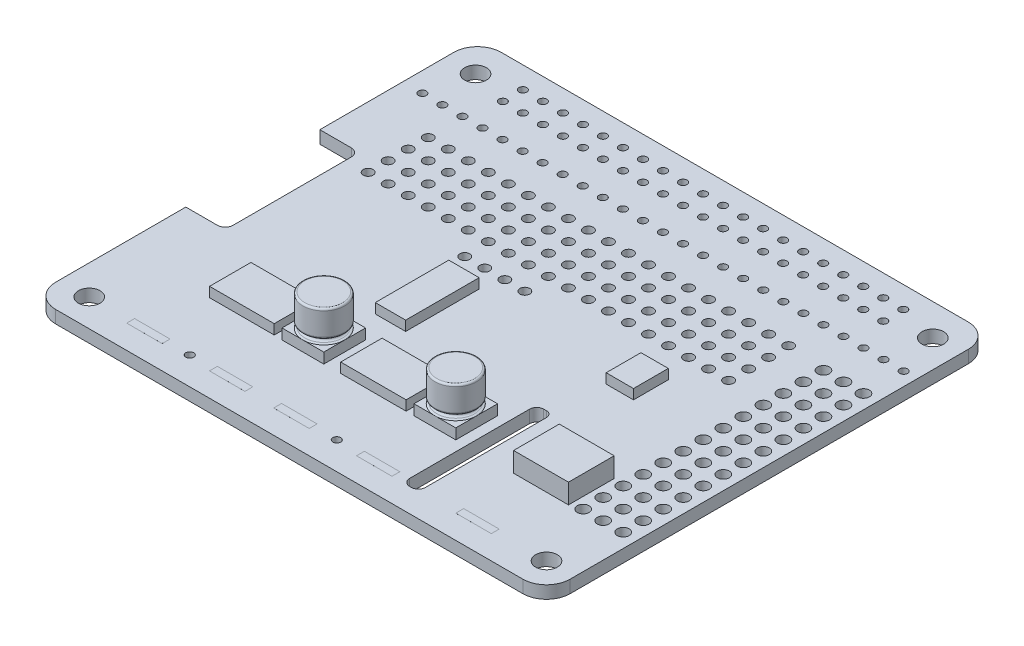
SolidWorks part; units mm, degrees
ref_plane "Front Plane" through (0, 0, 0) normal (0, 0, 1) x (1, 0, 0)
ref_plane "Top Plane" through (0, 0, 0) normal (0, 1, 0) x (1, 0, 0)
ref_plane "Right Plane" through (0, 0, 0) normal (1, 0, 0) x (0, 0, -1)
sketch "Sketch1" plane through (0, 0, 0) normal (0, 1, 0) x (1, 0, 0)
  line L1 (-72.0204, 27.4034) -> (-12.7704, 27.4034)
  line L2 (-75.0204, 24.4034) -> (-75.0204, -26.0966)
  line L3 (-72.0204, -29.0966) -> (-12.7704, -29.0966)
  line L4 (-9.7704, 24.4034) -> (-9.7704, -26.0966)
  line L5 (-75.0204, 7.4034) -> (-71.0204, 7.4034)
  line L6 (-75.0204, 7.4034) -> (-75.0204, -9.5966)
  line L7 (-75.0204, -9.5966) -> (-71.0204, -9.5966)
  line L8 (-70.0204, 6.4034) -> (-70.0204, -8.5966)
  line L9 (-29.7669, -9.0966) -> (-30.1204, -9.0966)
  line L10 (-29.0204, -9.8431) -> (-29.0204, -25.1966)
  line L11 (-29.9204, -26.0966) -> (-30.1204, -26.0966)
  line L12 (-31.0204, -9.9966) -> (-31.0204, -25.1966)
  arc A0 (-72.0204, -29.0966) -> (-75.0204, -26.0966) centre (-72.0204, -26.0966) cw
  arc A1 (-9.7704, -26.0966) -> (-12.7704, -29.0966) centre (-12.7704, -26.0966) cw
  arc A2 (-9.7704, 24.4034) -> (-12.7704, 27.4034) centre (-12.7704, 24.4034) ccw
  arc A3 (-72.0204, 27.4034) -> (-75.0204, 24.4034) centre (-72.0204, 24.4034) ccw
  arc A4 (-70.0204, -8.5966) -> (-71.0204, -9.5966) centre (-71.0204, -8.5966) cw
  arc A5 (-70.0204, 6.4034) -> (-71.0204, 7.4034) centre (-71.0204, 6.4034) ccw
  arc A6 (-29.0204, -25.1966) -> (-29.9204, -26.0966) centre (-29.9204, -25.1966) cw
  arc A7 (-30.1204, -26.0966) -> (-31.0204, -25.1966) centre (-30.1204, -25.1966) cw
  arc A8 (-30.1204, -9.0966) -> (-31.0204, -9.9966) centre (-30.1204, -9.9966) ccw
  arc A9 (-29.7669, -9.0966) -> (-29.0204, -9.8431) centre (-29.7669, -9.8431) cw
  circle A10 centre (-13.2704, -25.5966) radius 1.375
  circle A11 centre (-71.2704, -25.5966) radius 1.375
  circle A12 centre (-71.2704, 23.4034) radius 1.375
  circle A13 centre (-13.2704, 23.4034) radius 1.375
  point P6 (-75.0204, -29.0966)
  point P11 (-9.7704, 27.4034)
  point P14 (-75.0204, 27.4034)
  point P23 (-70.0204, 7.4034)
  point P30 (-29.0204, -26.0966)
  point P35 (-31.0204, -9.0966)
  point P38 (-29.0204, -9.0966)
  dimension "D3" = 3
  dimension "D7" = 1
  dimension "D12" = 0.9
  dimension "D13" = 0.7465
  dimension "D14" = 2.75
  dimension "D1" = 56.5
  dimension "D2" = 65.25
  dimension "D4" = 17
  dimension "D5" = 5
  dimension "D6" = 20
  dimension "D8" = 17
  dimension "D9" = 2
  dimension "D10" = 44
  dimension "D11" = 3
  dimension "D15" = 3.5
  dimension "D16" = 3.5
  dimension "D17" = 2
  dimension "D18" = 2
extrude "Board" add sketch "Sketch1" along normal blind 1.6 contours A5 L8 A4 L7 L2 A0 L3 A1 L4 A2 L1 A3 L5 A13 A12 A11 A10 L9 A9 L10 A6 L11 A7 L12 A8 region at (-41.7924, 0, 0.6811)
sketch "Sketch2" plane through (0, 1.6, 0) normal (0, 1, 0) x (1, 0, 0)
  line L8 (-70.0204, 6.4034) -> (-70.0204, -8.5966)
  line L9 (-71.0204, -9.5966) -> (-75.0204, -9.5966)
  line L10 (-75.0204, -9.5966) -> (-75.0204, -26.0966)
  line L11 (-72.0204, -29.0966) -> (-12.7704, -29.0966)
  line L12 (-9.7704, -26.0966) -> (-9.7704, 24.4034)
  line L13 (-12.7704, 27.4034) -> (-72.0204, 27.4034)
  line L14 (-75.0204, 24.4034) -> (-75.0204, 7.4034)
  line L15 (-75.0204, 7.4034) -> (-71.0204, 7.4034)
  line L16 (-70.0204, 6.4034) -> (-70.0204, -8.5966)
  line L17 (-71.0204, -9.5966) -> (-75.0204, -9.5966)
  line L18 (-75.0204, -9.5966) -> (-75.0204, -26.0966)
  line L19 (-72.0204, -29.0966) -> (-12.7704, -29.0966)
  line L20 (-9.7704, -26.0966) -> (-9.7704, 24.4034)
  line L21 (-12.7704, 27.4034) -> (-72.0204, 27.4034)
  line L22 (-75.0204, 24.4034) -> (-75.0204, 7.4034)
  line L23 (-75.0204, 7.4034) -> (-71.0204, 7.4034)
  circle A0 centre (-66.5204, 24.6534) radius 0.5
  circle A1 centre (-63.9804, 24.6534) radius 0.5
  circle A2 centre (-61.4404, 24.6534) radius 0.5
  circle A3 centre (-58.9004, 24.6534) radius 0.5
  circle A4 centre (-56.3604, 24.6534) radius 0.5
  circle A5 centre (-53.8204, 24.6534) radius 0.5
  arc A6 (-70.0204, 6.4034) -> (-71.0204, 7.4034) centre (-71.0204, 6.4034) ccw
  arc A7 (-71.0204, -9.5966) -> (-70.0204, -8.5966) centre (-71.0204, -8.5966) ccw
  arc A8 (-75.0204, -26.0966) -> (-72.0204, -29.0966) centre (-72.0204, -26.0966) ccw
  arc A9 (-12.7704, -29.0966) -> (-9.7704, -26.0966) centre (-12.7704, -26.0966) ccw
  arc A10 (-9.7704, 24.4034) -> (-12.7704, 27.4034) centre (-12.7704, 24.4034) ccw
  arc A11 (-72.0204, 27.4034) -> (-75.0204, 24.4034) centre (-72.0204, 24.4034) ccw
  arc A12 (-70.0204, 6.4034) -> (-71.0204, 7.4034) centre (-71.0204, 6.4034) ccw
  arc A13 (-71.0204, -9.5966) -> (-70.0204, -8.5966) centre (-71.0204, -8.5966) ccw
  arc A14 (-75.0204, -26.0966) -> (-72.0204, -29.0966) centre (-72.0204, -26.0966) ccw
  arc A15 (-12.7704, -29.0966) -> (-9.7704, -26.0966) centre (-12.7704, -26.0966) ccw
  arc A16 (-9.7704, 24.4034) -> (-12.7704, 27.4034) centre (-12.7704, 24.4034) ccw
  arc A17 (-72.0204, 27.4034) -> (-75.0204, 24.4034) centre (-72.0204, 24.4034) ccw
  circle A18 centre (-51.2804, 24.6534) radius 0.5
  circle A19 centre (-48.7404, 24.6534) radius 0.5
  circle A20 centre (-46.2004, 24.6534) radius 0.5
  circle A21 centre (-43.6604, 24.6534) radius 0.5
  circle A22 centre (-41.1204, 24.6534) radius 0.5
  circle A23 centre (-38.5804, 24.6534) radius 0.5
  circle A24 centre (-36.0404, 24.6534) radius 0.5
  circle A25 centre (-33.5004, 24.6534) radius 0.5
  circle A26 centre (-30.9604, 24.6534) radius 0.5
  circle A27 centre (-28.4204, 24.6534) radius 0.5
  circle A28 centre (-25.8804, 24.6534) radius 0.5
  circle A29 centre (-23.3404, 24.6534) radius 0.5
  circle A30 centre (-20.8004, 24.6534) radius 0.5
  circle A31 centre (-18.2604, 24.6534) radius 0.5
  circle A32 centre (-63.9804, 22.1134) radius 0.5
  circle A33 centre (-61.4404, 22.1134) radius 0.5
  circle A34 centre (-58.9004, 22.1134) radius 0.5
  circle A35 centre (-56.3604, 22.1134) radius 0.5
  circle A36 centre (-53.8204, 22.1134) radius 0.5
  circle A37 centre (-51.2804, 22.1134) radius 0.5
  circle A38 centre (-48.7404, 22.1134) radius 0.5
  circle A39 centre (-46.2004, 22.1134) radius 0.5
  circle A40 centre (-43.6604, 22.1134) radius 0.5
  circle A41 centre (-41.1204, 22.1134) radius 0.5
  circle A42 centre (-38.5804, 22.1134) radius 0.5
  circle A43 centre (-36.0404, 22.1134) radius 0.5
  circle A44 centre (-33.5004, 22.1134) radius 0.5
  circle A45 centre (-30.9604, 22.1134) radius 0.5
  circle A46 centre (-28.4204, 22.1134) radius 0.5
  circle A47 centre (-25.8804, 22.1134) radius 0.5
  circle A48 centre (-23.3404, 22.1134) radius 0.5
  circle A49 centre (-20.8004, 22.1134) radius 0.5
  circle A50 centre (-18.2604, 22.1134) radius 0.5
  circle A51 centre (-66.5204, 22.1134) radius 0.5
  circle A52 centre (-72.5204, 17.9034) radius 0.5
  circle A53 centre (-69.9766, 17.9034) radius 0.5
  circle A54 centre (-67.4329, 17.9034) radius 0.5
  circle A55 centre (-64.8891, 17.9034) radius 0.5
  circle A56 centre (-62.3454, 17.9034) radius 0.5
  circle A57 centre (-59.8016, 17.9034) radius 0.5
  circle A58 centre (-57.2579, 17.9034) radius 0.5
  circle A59 centre (-54.7141, 17.9034) radius 0.5
  circle A60 centre (-52.1704, 17.9034) radius 0.5
  circle A61 centre (-49.6266, 17.9034) radius 0.5
  circle A62 centre (-47.0829, 17.9034) radius 0.5
  circle A63 centre (-44.5391, 17.9034) radius 0.5
  circle A64 centre (-41.9954, 17.9034) radius 0.5
  circle A65 centre (-39.4516, 17.9034) radius 0.5
  circle A66 centre (-36.9079, 17.9034) radius 0.5
  circle A67 centre (-34.3641, 17.9034) radius 0.5
  circle A68 centre (-31.8204, 17.9034) radius 0.5
  circle A69 centre (-29.2766, 17.9034) radius 0.5
  circle A70 centre (-26.7329, 17.9034) radius 0.5
  circle A71 centre (-24.1891, 17.9034) radius 0.5
  circle A72 centre (-21.6454, 17.9034) radius 0.5
  circle A73 centre (-19.1016, 17.9034) radius 0.5
  circle A74 centre (-16.5579, 17.9034) radius 0.5
  circle A75 centre (-14.0141, 17.9034) radius 0.5
  circle A76 centre (-11.4704, 17.9034) radius 0.5
  circle A77 centre (-11.5604, 12.9034) radius 0.75
  circle A78 centre (-14.1004, 12.9034) radius 0.75
  circle A79 centre (-16.6404, 12.9034) radius 0.75
  circle A80 centre (-14.1004, 10.3634) radius 0.75
  circle A81 centre (-16.6404, 10.3634) radius 0.75
  circle A82 centre (-14.1004, 7.8234) radius 0.75
  circle A83 centre (-16.6404, 7.8234) radius 0.75
  circle A84 centre (-14.1004, 5.2834) radius 0.75
  circle A85 centre (-16.6404, 5.2834) radius 0.75
  circle A86 centre (-14.1004, 2.7434) radius 0.75
  circle A87 centre (-16.6404, 2.7434) radius 0.75
  circle A88 centre (-14.1004, 0.2034) radius 0.75
  circle A89 centre (-16.6404, 0.2034) radius 0.75
  circle A90 centre (-14.1004, -2.3366) radius 0.75
  circle A91 centre (-16.6404, -2.3366) radius 0.75
  circle A92 centre (-14.1004, -4.8766) radius 0.75
  circle A93 centre (-16.6404, -4.8766) radius 0.75
  circle A94 centre (-14.1004, -7.4166) radius 0.75
  circle A95 centre (-16.6404, -7.4166) radius 0.75
  circle A96 centre (-14.1004, -9.9566) radius 0.75
  circle A97 centre (-16.6404, -9.9566) radius 0.75
  circle A98 centre (-14.1004, -12.4966) radius 0.75
  circle A99 centre (-16.6404, -12.4966) radius 0.75
  circle A100 centre (-14.1004, -15.0366) radius 0.75
  circle A101 centre (-16.6404, -15.0366) radius 0.75
  circle A102 centre (-14.1004, -17.5766) radius 0.75
  circle A103 centre (-16.6404, -17.5766) radius 0.75
  circle A104 centre (-11.5604, 10.3634) radius 0.75
  circle A105 centre (-11.5604, 7.8234) radius 0.75
  circle A106 centre (-11.5604, 5.2834) radius 0.75
  circle A107 centre (-11.5604, 2.7434) radius 0.75
  circle A108 centre (-11.5604, 0.2034) radius 0.75
  circle A109 centre (-11.5604, -2.3366) radius 0.75
  circle A110 centre (-11.5604, -4.8766) radius 0.75
  circle A111 centre (-11.5604, -7.4166) radius 0.75
  circle A112 centre (-11.5604, -9.9566) radius 0.75
  circle A113 centre (-11.5604, -12.4966) radius 0.75
  circle A114 centre (-11.5604, -15.0366) radius 0.75
  circle A115 centre (-11.5604, -17.5766) radius 0.75
  circle A116 centre (-67.2704, 13.4034) radius 0.625
  circle A117 centre (-64.7304, 13.4034) radius 0.625
  circle A118 centre (-62.1904, 13.4034) radius 0.625
  circle A119 centre (-59.6504, 13.4034) radius 0.625
  circle A120 centre (-57.1104, 13.4034) radius 0.625
  circle A121 centre (-54.5704, 13.4034) radius 0.625
  circle A122 centre (-52.0304, 13.4034) radius 0.625
  circle A123 centre (-49.4904, 13.4034) radius 0.625
  circle A124 centre (-46.9504, 13.4034) radius 0.625
  circle A125 centre (-44.4104, 13.4034) radius 0.625
  circle A126 centre (-41.8704, 13.4034) radius 0.625
  circle A127 centre (-39.3304, 13.4034) radius 0.625
  circle A128 centre (-36.7904, 13.4034) radius 0.625
  circle A129 centre (-34.2504, 13.4034) radius 0.625
  circle A130 centre (-31.7104, 13.4034) radius 0.625
  circle A131 centre (-29.1704, 13.4034) radius 0.625
  circle A132 centre (-26.6304, 13.4034) radius 0.625
  circle A133 centre (-24.0904, 13.4034) radius 0.625
  circle A134 centre (-21.5504, 13.4034) radius 0.625
  circle A135 centre (-64.7304, 10.8634) radius 0.625
  circle A136 centre (-62.1904, 10.8634) radius 0.625
  circle A137 centre (-59.6504, 10.8634) radius 0.625
  circle A138 centre (-57.1104, 10.8634) radius 0.625
  circle A139 centre (-54.5704, 10.8634) radius 0.625
  circle A140 centre (-52.0304, 10.8634) radius 0.625
  circle A141 centre (-49.4904, 10.8634) radius 0.625
  circle A142 centre (-46.9504, 10.8634) radius 0.625
  circle A143 centre (-44.4104, 10.8634) radius 0.625
  circle A144 centre (-41.8704, 10.8634) radius 0.625
  circle A145 centre (-39.3304, 10.8634) radius 0.625
  circle A146 centre (-36.7904, 10.8634) radius 0.625
  circle A147 centre (-34.2504, 10.8634) radius 0.625
  circle A148 centre (-31.7104, 10.8634) radius 0.625
  circle A149 centre (-29.1704, 10.8634) radius 0.625
  circle A150 centre (-26.6304, 10.8634) radius 0.625
  circle A151 centre (-24.0904, 10.8634) radius 0.625
  circle A152 centre (-21.5504, 10.8634) radius 0.625
  circle A153 centre (-64.7304, 8.3234) radius 0.625
  circle A154 centre (-62.1904, 8.3234) radius 0.625
  circle A155 centre (-59.6504, 8.3234) radius 0.625
  circle A156 centre (-57.1104, 8.3234) radius 0.625
  circle A157 centre (-54.5704, 8.3234) radius 0.625
  circle A158 centre (-52.0304, 8.3234) radius 0.625
  circle A159 centre (-49.4904, 8.3234) radius 0.625
  circle A160 centre (-46.9504, 8.3234) radius 0.625
  circle A161 centre (-44.4104, 8.3234) radius 0.625
  circle A162 centre (-41.8704, 8.3234) radius 0.625
  circle A163 centre (-39.3304, 8.3234) radius 0.625
  circle A164 centre (-36.7904, 8.3234) radius 0.625
  circle A165 centre (-34.2504, 8.3234) radius 0.625
  circle A166 centre (-31.7104, 8.3234) radius 0.625
  circle A167 centre (-29.1704, 8.3234) radius 0.625
  circle A168 centre (-26.6304, 8.3234) radius 0.625
  circle A169 centre (-24.0904, 8.3234) radius 0.625
  circle A170 centre (-21.5504, 8.3234) radius 0.625
  circle A171 centre (-64.7304, 5.7834) radius 0.625
  circle A172 centre (-62.1904, 5.7834) radius 0.625
  circle A173 centre (-59.6504, 5.7834) radius 0.625
  circle A174 centre (-57.1104, 5.7834) radius 0.625
  circle A175 centre (-54.5704, 5.7834) radius 0.625
  circle A176 centre (-52.0304, 5.7834) radius 0.625
  circle A177 centre (-49.4904, 5.7834) radius 0.625
  circle A178 centre (-46.9504, 5.7834) radius 0.625
  circle A179 centre (-44.4104, 5.7834) radius 0.625
  circle A180 centre (-41.8704, 5.7834) radius 0.625
  circle A181 centre (-39.3304, 5.7834) radius 0.625
  circle A182 centre (-36.7904, 5.7834) radius 0.625
  circle A183 centre (-34.2504, 5.7834) radius 0.625
  circle A184 centre (-31.7104, 5.7834) radius 0.625
  circle A185 centre (-29.1704, 5.7834) radius 0.625
  circle A186 centre (-26.6304, 5.7834) radius 0.625
  circle A187 centre (-24.0904, 5.7834) radius 0.625
  circle A188 centre (-21.5504, 5.7834) radius 0.625
  circle A189 centre (-67.2704, 10.8634) radius 0.625
  circle A190 centre (-67.2704, 8.3234) radius 0.625
  circle A191 centre (-67.2704, 5.7834) radius 0.625
  circle A192 centre (-44.2704, 2.6534) radius 0.625
  circle A193 centre (-46.8104, 2.6534) radius 0.625
  circle A194 centre (-49.3504, 2.6534) radius 0.625
  circle A195 centre (-51.8904, 2.6534) radius 0.625
  circle A196 centre (-20.2704, -25.5966) radius 0.5
  circle A197 centre (-23.7704, -25.5966) radius 0.5
  circle A198 centre (-32.8704, -25.5966) radius 0.5
  circle A199 centre (-36.3704, -25.5966) radius 0.5
  circle A200 centre (-39.8704, -25.5966) radius 0.5
  circle A201 centre (-43.3704, -25.5966) radius 0.5
  circle A202 centre (-46.8704, -25.5966) radius 0.5
  circle A203 centre (-65.5204, -25.5966) radius 0.5
  circle A204 centre (-62.0204, -25.5966) radius 0.5
  circle A205 centre (-58.5204, -25.5966) radius 0.5
  circle A206 centre (-55.0204, -25.5966) radius 0.5
  circle A207 centre (-51.5204, -25.5966) radius 0.5
  dimension "D2" = 2.75
  dimension "D6" = 2.5
  dimension "D9" = 1.5
  dimension "D12" = 3
  dimension "D14" = 14
  dimension "D18" = 34.5
  dimension "D21" = 3.5
  dimension "D24" = 3.5
  dimension "D27" = 9.5
  dimension "D3" = 8.5
  dimension "D7" = 10.5
  dimension "D10" = 14.5
  dimension "D11" = 1.7
  dimension "D15" = 2.75
  dimension "D19" = 31.75
  dimension "D22" = 10.5
  dimension "D25" = 23.1
  dimension "D28" = 3.5
  dimension "D1" = 0
  dimension "D4" = 20
  dimension "D5" = 2
  dimension "D8" = 25
  dimension "D13" = 13
  dimension "D16" = 19
  dimension "D17" = 4
  dimension "D20" = 4
  dimension "D23" = 2
  dimension "D26" = 5
  dimension "D29" = 5
extrude "Some Holes" cut sketch "Sketch2" against normal blind 1.6 contours A114 | A83 | A103 | A102 | A115 | A100 | A101 | A99 | A98 | A113 | A112 | A96 | A97 | A95 | A94 | A111 | A110 | A92 | A93 | A91 | A90 | A109 | A108 | A88 | A89 | A87 | A86 | A107 | A106 | A84 | A85 | A82 | A105 | A104 | A77 | A80 | A81 | A79 | A78 | A76 | A75 | A74 | A73 | A72 | A50 | A31 | A49 | A30 | A48 | A29 | A71 | A70 | A47 | A28 | A27 | A46 | A69 | A68 | A45 | A26 | A67 | A44 | A25 | A66 | A43 | A24 | A65 | A42 | A23 | A64 | A41 | A22 | A63 | A40 | A21 | A20 | A39 | A62 | A61 | A38 | A19 | A18 | A37 | A60 | A59 | A36 | A5 | A4 | A35 | A58 | A57 | A34 | A3 | A2 | A33 | A56 | A55 | A32 | A1 | A0 region at (-16.6404, 1.6, -7.8234) region at (-11.5604, 1.6, 15.0366)
extrude "Remaining Holes" cut sketch "Sketch2<4>" against normal blind 1.6 contours A51 | A54 | A53 | A52 | A116 | A117 | A118 | A119 | A120 | A121 | A122 | A123 | A124 | A125 | A126 | A127 | A128 | A129 | A130 | A131 | A132 | A133 | A134 | A152 | A170 | A188 | A187 | A169 | A151 | A150 | A168 | A186 | A167 | A185 | A149 | A148 | A166 | A184 | A183 | A165 | A147 | A146 | A164 | A182 | A181 | A163 | A145 | A144 | A162 | A180 | A192 | A193 | A194 | A195 | A179 | A161 | A143 | A142 | A160 | A178 | A177 | A159 | A141 | A140 | A158 | A176 | A175 | A157 | A139 | A138 | A156 | A174 | A173 | A155 | A137 | A136 | A154 | A172 | A171 | A153 | A135 | A189 | A190 | A191 | A196 | A197 | A198 | A199 | A200 | A201 | A202 | A207 | A206 | A205 | A204 | A203
sketch "Sketch2<4>" plane through (0, 1.6, 0) normal (0, 1, 0) x (1, 0, 0) same geometry as "Sketch2"
sketch "Sketch3" plane through (0, 1.6, 0) normal (0, 1, 0) x (1, 0, 0)
  line L1 (-63.5566, -12.7994) -> (-55.3553, -12.7994)
  line L2 (-63.5566, -12.7994) -> (-63.5566, -18.049)
  line L3 (-63.5566, -18.049) -> (-55.3553, -18.049)
  line L4 (-55.3553, -12.7994) -> (-55.3553, -18.049)
  line L5 (-46.9235, -12.7994) -> (-38.6242, -12.7994)
  line L6 (-46.9235, -12.7994) -> (-46.9235, -18.049)
  line L7 (-46.9235, -18.049) -> (-38.6242, -18.049)
  line L8 (-38.6242, -12.7994) -> (-38.6242, -18.049)
  line L9 (-24.9943, -12.2493) -> (-18.0305, -12.2493)
  line L10 (-24.9943, -12.2493) -> (-24.9943, -18.049)
  line L11 (-24.9943, -18.049) -> (-18.0305, -18.049)
  line L12 (-18.0305, -12.2493) -> (-18.0305, -18.049)
  line L13 (-28.9097, 2.0257) -> (-25.4441, 2.0257)
  line L14 (-28.9097, 2.0257) -> (-28.9097, -2.3878)
  line L15 (-28.9097, -2.3878) -> (-25.4441, -2.3878)
  line L16 (-25.4441, 2.0257) -> (-25.4441, -2.3878)
  line L17 (-51.2629, 0) -> (-47.4092, 0)
  line L18 (-51.2629, 0) -> (-51.2629, -9.3248)
  line L19 (-51.2629, -9.3248) -> (-47.4092, -9.3248)
  line L20 (-47.4092, 0) -> (-47.4092, -9.3248)
  dimension "D1" = 5.2496
  dimension "D2" = 8.2013
  dimension "D3" = 5.2496
  dimension "D4" = 8.2993
  dimension "D5" = 5.7997
  dimension "D6" = 6.9638
  dimension "D7" = 4.4135
  dimension "D8" = 3.4656
  dimension "D9" = 9.3248
  dimension "D10" = 3.8537
extrude "ICs" add sketch "Sketch3" along normal blind 1.25 contours L8 L5 L6 L7 | L4 L1 L2 L3 | L16 L13 L14 L15 | L18 L17 L20 L19 region at (-59.456, 1.6, 15.4242) region at (-42.7739, 1.6, 15.4242) region at (-27.1769, 1.6, 0.181)
extrude "Voltage Regulator" add sketch "Sketch3<5>" along normal blind 2.5 contours L11 L12 L9 L10
sketch "Sketch3<5>" plane through (0, 1.6, 0) normal (0, 1, 0) x (1, 0, 0) same geometry as "Sketch3"
sketch "Sketch4" plane through (0, 1.6, 0) normal (0, 1, 0) x (1, 0, 0)
  line L0 (-31.0204, -9.9966) -> (-31.0204, -25.1966) construction
  line L1 (-54.3204, -18.0966) -> (-49.0204, -18.0966)
  line L2 (-54.3204, -18.0966) -> (-54.3204, -12.7966)
  line L3 (-54.3204, -12.7966) -> (-49.0204, -12.7966)
  line L4 (-49.0204, -18.0966) -> (-49.0204, -12.7966)
  line L5 (-32.3204, -18.0544) -> (-37.6204, -18.0544)
  line L6 (-32.3204, -18.0544) -> (-32.3204, -12.7544)
  line L7 (-32.3204, -12.7544) -> (-37.6204, -12.7544)
  line L8 (-37.6204, -18.0544) -> (-37.6204, -12.7544)
  line L9 (-72.0204, -29.0966) -> (-12.7704, -29.0966) construction
  dimension "D1" = 5.3
  dimension "D2" = 5.3
  dimension "D3" = 5.3
  dimension "D4" = 5.3
  dimension "D5" = 11.4
  dimension "D6" = 1.3
  dimension "D7" = 11
extrude "Cap Base" add sketch "Sketch4" along normal blind 1.32
sketch "Sketch5" plane through (0, 2.92, 0) normal (0, 1, 0) x (1, 0, 0)
  line L0 (-54.3204, -15.4466) -> (-49.0204, -15.4466)
  line L1 (-51.6704, -12.7966) -> (-51.6704, -18.0966)
  line L2 (-34.9704, -12.7544) -> (-34.9704, -18.0544)
  line L3 (-37.6204, -15.4044) -> (-32.3204, -15.4044)
  line L4 (-54.3204, -12.7966) -> (-54.3204, -18.0966)
  line L5 (-54.3204, -18.0966) -> (-49.0204, -18.0966)
  line L6 (-49.0204, -18.0966) -> (-49.0204, -12.7966)
  line L7 (-49.0204, -12.7966) -> (-54.3204, -12.7966)
  line L8 (-54.3204, -12.7966) -> (-54.3204, -18.0966)
  line L9 (-54.3204, -18.0966) -> (-49.0204, -18.0966)
  line L10 (-49.0204, -18.0966) -> (-49.0204, -12.7966)
  line L11 (-49.0204, -12.7966) -> (-54.3204, -12.7966)
  line L12 (-32.3204, -18.0544) -> (-32.3204, -12.7544)
  line L13 (-32.3204, -12.7544) -> (-37.6204, -12.7544)
  line L14 (-37.6204, -12.7544) -> (-37.6204, -18.0544)
  line L15 (-37.6204, -18.0544) -> (-32.3204, -18.0544)
  line L16 (-32.3204, -18.0544) -> (-32.3204, -12.7544)
  line L17 (-32.3204, -12.7544) -> (-37.6204, -12.7544)
  line L18 (-37.6204, -12.7544) -> (-37.6204, -18.0544)
  line L19 (-37.6204, -18.0544) -> (-32.3204, -18.0544)
  circle A0 centre (-51.6704, -15.4466) radius 2.65
  circle A1 centre (-34.9704, -15.4044) radius 2.65
  line M9 (-54.3204, -12.7966) -> (-54.3204, -18.0966)
  line M10 (-54.3204, -18.0966) -> (-49.0204, -18.0966)
  dimension "D1" = 0
  dimension "D2" = 0
extrude "Cap1" add sketch "Sketch5" along normal blind 0.1 contours L1 A0 L0 | L0 A0 L1 | A0 L10 L0 L1 M10 | A0 L9 L1 L0 M9 | L2 A1 L3 | L3 A1 L2 | L19 A1 L16 L3 L2 | L18 A1 L19 L2 L3 region at (-52.7951, 2.92, 14.3219) region at (-52.7951, 2.92, 16.5713) region at (-50.5457, 2.92, 14.3219) region at (-50.5457, 2.92, 16.5713) region at (-33.8457, 2.92, 14.2797) region at (-36.0951, 2.92, 14.2797) region at (-33.8457, 2.92, 16.5291) region at (-36.0951, 2.92, 16.5291)
sketch "Sketch8" plane through (0, 3.02, 0) normal (0, 1, 0) x (1, 0, 0)
  circle A0 centre (-34.9704, -15.4044) radius 2.65 construction
  circle A1 centre (-51.6704, -15.4466) radius 2.65 construction
  circle A2 centre (-34.9704, -15.4044) radius 2.65
  circle A3 centre (-51.6704, -15.4466) radius 2.65
  circle A4 centre (-51.6704, -15.4466) radius 2.15
  circle A5 centre (-34.9704, -15.4044) radius 2.15
extrude "Cap2" add sketch "Sketch8" along normal blind 0.5 contours A5 | A4 | A5 region at (-34.9704, 3.02, 15.4044)
sketch "Sketch9" plane through (0, 3.52, 0) normal (0, 1, 0) x (1, 0, 0)
  circle A0 centre (-34.9704, -15.4044) radius 2.15 construction
  circle A1 centre (-51.6704, -15.4466) radius 2.15 construction
  circle A2 centre (-34.9704, -15.4044) radius 2.65 construction
  circle A3 centre (-51.6704, -15.4466) radius 2.65 construction
  circle A4 centre (-34.9704, -15.4044) radius 2.15
  circle A5 centre (-51.6704, -15.4466) radius 2.15
  circle A6 centre (-34.9704, -15.4044) radius 2.65
  circle A7 centre (-51.6704, -15.4466) radius 2.65
  circle A8 centre (-51.6704, -15.4466) radius 2.65
  circle A9 centre (-34.9704, -15.4044) radius 2.65
  circle M1 centre (-51.6704, -15.4466) radius 2.15
extrude "Cap3" add sketch "Sketch9" along normal blind 3.38 contours M1 | A7 M1 | A4 | A6 A4 region at (-34.9704, 3.52, 15.4044) region at (-51.6704, 3.52, 15.4466) region at (-37.5454, 3.52, 15.4044) region at (-54.2454, 3.52, 15.4466)
fillet "Cap4" radius 0.24 2 edges at (-51.6704, 6.9, 18.0966) (-34.9704, 6.9, 18.0544)
fillet "Cap5" radius 0.25 4 edges at (-34.9704, 3.52, 17.5544) (-34.9704, 3.02, 17.5544) (-51.6704, 3.52, 17.5966) (-51.6704, 3.02, 17.5966)
fillet "Cap6" radius 0.25 2 edges at (-34.9704, 3.52, 18.0544) (-51.6704, 3.52, 18.0966)
fillet "Cap7" radius 0.1 2 edges at (-51.6704, 3.02, 18.0966) (-34.9704, 3.02, 18.0544) second distance 0.25 first distance on face at (-51.6704, 3.02, 18.0966) first distance on face at (-34.9704, 3.02, 18.0544)
sketch "Skizze1" plane through (0, 1.6, 0) normal (0, 1, 0) x (1, 0, 0)
  line L1 (-24.2704, -25.0966) -> (-19.7704, -25.0966)
  line L2 (-24.2704, -25.0966) -> (-24.2704, -26.0966)
  line L3 (-24.2704, -26.0966) -> (-19.7704, -26.0966)
  line L4 (-19.7704, -25.0966) -> (-19.7704, -26.0966)
  line L5 (-47.3704, -25.0966) -> (-42.8704, -25.0966)
  line L6 (-47.3704, -25.0966) -> (-47.3704, -26.0966)
  line L7 (-47.3704, -26.0966) -> (-42.8704, -26.0966)
  line L8 (-42.8704, -25.0966) -> (-42.8704, -26.0966)
  line L9 (-36.8704, -25.0966) -> (-32.3704, -25.0966)
  line L10 (-36.8704, -25.0966) -> (-36.8704, -26.0966)
  line L11 (-36.8704, -26.0966) -> (-32.3704, -26.0966)
  line L12 (-32.3704, -25.0966) -> (-32.3704, -26.0966)
  line L13 (-55.5204, -25.0966) -> (-51.0204, -25.0966)
  line L14 (-55.5204, -25.0966) -> (-55.5204, -26.0966)
  line L15 (-55.5204, -26.0966) -> (-51.0204, -26.0966)
  line L16 (-51.0204, -25.0966) -> (-51.0204, -26.0966)
  line L17 (-66.0204, -25.0966) -> (-61.5204, -25.0966)
  line L18 (-66.0204, -25.0966) -> (-66.0204, -26.0966)
  line L19 (-66.0204, -26.0966) -> (-61.5204, -26.0966)
  line L20 (-61.5204, -25.0966) -> (-61.5204, -26.0966)
  circle A0 centre (-65.5204, -25.5966) radius 0.5 construction
  circle A1 centre (-62.0204, -25.5966) radius 0.5 construction
  circle A2 centre (-55.0204, -25.5966) radius 0.5 construction
  circle A3 centre (-51.5204, -25.5966) radius 0.5 construction
  circle A4 centre (-46.8704, -25.5966) radius 0.5 construction
  circle A5 centre (-43.3704, -25.5966) radius 0.5 construction
  circle A6 centre (-32.8704, -25.5966) radius 0.5 construction
  circle A7 centre (-36.3704, -25.5966) radius 0.5 construction
  circle A8 centre (-23.7704, -25.5966) radius 0.5 construction
  circle A9 centre (-20.2704, -25.5966) radius 0.5 construction
extrude "Aufsatz-Linear austragen5" add sketch "Skizze1" against normal up to surface (1.6 mm away) and the other way blind 0.001 from surface up to face at (-66.5204, 0, -21.6134) starting at face at (-27.1769, 1.6, 0.181)
